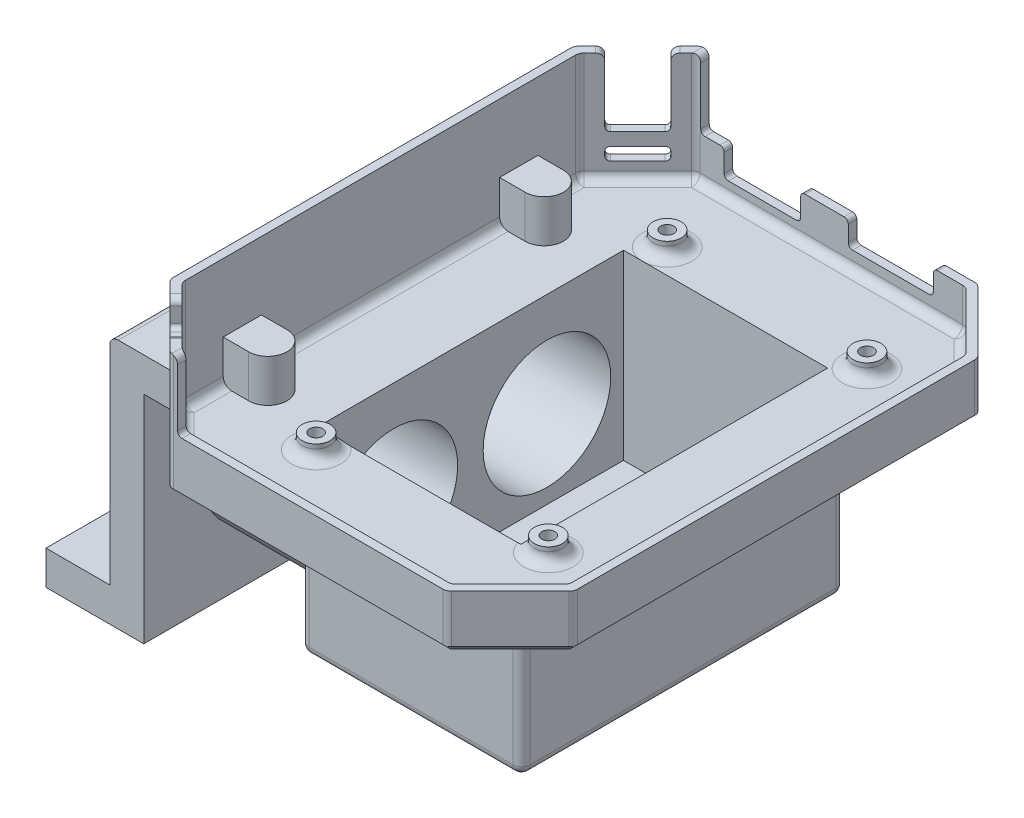
SolidWorks part; units mm, degrees
ref_plane "Front Plane" through (0, 0, 0) normal (0, 0, 1) x (1, 0, 0)
ref_plane "Top Plane" through (0, 0, 0) normal (0, 1, 0) x (1, 0, 0)
ref_plane "Right Plane" through (0, 0, 0) normal (1, 0, 0) x (0, 0, -1)
sketch "Skica1" plane through (0, 0, 0) normal (0, 1, 0) x (1, 0, 0)
  line L1 (0, 0) -> (95, 0)
  line L2 (0, 0) -> (0, 125)
  line L3 (0, 125) -> (95, 125)
  line L4 (95, 0) -> (95, 125)
  dimension "D1" = 125
  dimension "D2" = 95
extrude "Přidat vysunutím1" add sketch "Skica1" along normal blind 2.8
chamfer "Zkosení1" distance 15 angle 45 4 edges at (95, 1.4, -125) (95, 1.4, 0) (0, 1.4, 0) (0, 1.4, -125)
sketch "Skica2" plane through (0, 2.8, 0) normal (0, 1, 0) x (1, 0, 0)
  line L0 (93, 15.8284) -> (93, 109.1716)
  line L1 (93, 109.1716) -> (79.1716, 123)
  line L2 (79.1716, 123) -> (15.8284, 123)
  line L3 (15.8284, 123) -> (2, 109.1716)
  line L4 (2, 109.1716) -> (2, 15.8284)
  line L5 (2, 15.8284) -> (15.8284, 2)
  line L6 (15.8284, 2) -> (79.1716, 2)
  line L7 (79.1716, 2) -> (93, 15.8284)
  line L8 (95, 15) -> (95, 110)
  line L9 (95, 110) -> (80, 125)
  line L10 (80, 125) -> (15, 125)
  line L11 (15, 125) -> (0, 110)
  line L12 (0, 110) -> (0, 15)
  line L13 (0, 15) -> (15, 0)
  line L14 (15, 0) -> (80, 0)
  line L15 (80, 0) -> (95, 15)
  line L16 (95, 15) -> (95, 110)
  line L17 (95, 110) -> (80, 125)
  line L18 (80, 125) -> (15, 125)
  line L19 (15, 125) -> (0, 110)
  line L20 (0, 110) -> (0, 15)
  line L21 (0, 15) -> (15, 0)
  line L22 (15, 0) -> (80, 0)
  line L23 (80, 0) -> (95, 15)
  dimension "D1" = 0
  dimension "D2" = 2
extrude "Přidat vysunutím2" add sketch "Skica2" along normal blind 10
sketch "Skica3" plane through (0, 2.8, 0) normal (0, 1, 0) x (1, 0, 0)
  line L0 (50, 123) -> (50, 2) construction
  line L1 (23.33, 120) -> (76.67, 120) construction
  line L2 (23.33, 120) -> (23.33, 18.4) construction
  line L3 (23.33, 18.4) -> (76.67, 18.4) construction
  line L4 (76.67, 120) -> (76.67, 18.4) construction
  line L5 (23.33, 120) -> (76.67, 18.4) construction
  line L6 (23.33, 18.4) -> (76.67, 120) construction
  line L9 (0, 110) -> (0, 15) construction
  line L10 (79.1716, 123) -> (15.8284, 123) construction
  circle A0 centre (25.87, 106.03) radius 1.55
  circle A1 centre (74.13, 104.76) radius 1.55
  circle A2 centre (74.13, 29.83) radius 1.55
  circle A3 centre (30.95, 53.96) radius 1.55
  circle A4 centre (25.87, 23.48) radius 1.55
  point P0 (50, 69.2)
  dimension "D4" = 2.54
  dimension "D6" = 15.24
  dimension "D7" = 3.1
  dimension "D11" = 66.04
  dimension "D1" = 53.34
  dimension "D2" = 101.6
  dimension "D3" = 3
  dimension "D5" = 2.54
  dimension "D8" = 13.97
  dimension "D9" = 90.17
  dimension "D10" = 7.62
  dimension "D12" = 96.52
  dimension "D13" = 50
extrude "Odebrat vysunutím1" cut sketch "Skica3" against normal blind 10
chamfer "Zkosení2" distance 1.5 angle 45 8 edges at (87.5, 0, -117.5) (95, 0, -62.5) (87.5, 0, -7.5) (47.5, 0, 0) (7.5, 0, -7.5) (0, 0, -62.5) (7.5, 0, -117.5) (47.5, 0, -125)
fillet "Zaoblit1" radius 2 24 edges at (93, 7.8, -15.8284) (79.1716, 7.8, -2) (15.8284, 7.8, -2) (2, 7.8, -15.8284) (15.8284, 7.8, -123) (2, 7.8, -109.1716) (93, 7.8, -109.1716) (79.1716, 7.8, -123) (8.9142, 2.8, -8.9142) (47.5, 2.8, -2) (86.0858, 2.8, -8.9142) (93, 2.8, -62.5) (86.0858, 2.8, -116.0858) (47.5, 2.8, -123) (2, 2.8, -62.5) (8.9142, 2.8, -116.0858) (15, 7.15, 0) (0, 7.15, -15) (0, 7.15, -110) (15, 7.15, -125) (80, 7.15, -125) (95, 7.15, -110) (95, 7.15, -15) (80, 7.15, 0)
sketch "Skica5" plane through (0, 2.8, 0) normal (0, 1, 0) x (1, 0, 0)
  circle A0 centre (74.13, 29.83) radius 3.3
  circle A1 centre (25.87, 23.48) radius 3.3
  circle A2 centre (30.95, 53.96) radius 3.3
  circle A3 centre (25.87, 106.03) radius 3.3
  circle A4 centre (74.13, 104.76) radius 3.3
  circle A5 centre (25.87, 23.48) radius 1.55 construction
  circle A6 centre (74.13, 29.83) radius 1.55 construction
  circle A7 centre (30.95, 53.96) radius 1.55 construction
  circle A8 centre (25.87, 106.03) radius 1.55 construction
  circle A9 centre (74.13, 104.76) radius 1.55 construction
  circle A10 centre (25.87, 23.48) radius 1.55
  circle A11 centre (74.13, 29.83) radius 1.55
  circle A12 centre (30.95, 53.96) radius 1.55
  circle A13 centre (25.87, 106.03) radius 1.55
  circle A14 centre (74.13, 104.76) radius 1.55
  dimension "D1" = 6.6
extrude "Přidat vysunutím3" add sketch "Skica5" along normal blind 3.5
fillet "Zaoblit2" radius 2.5 5 edges at (74.13, 2.8, -108.06) (25.87, 2.8, -109.33) (30.95, 2.8, -57.26) (25.87, 2.8, -26.78) (74.13, 2.8, -33.13)
sketch "Skica6" plane through (0, 0, 0) normal (0, -1, 0) x (1, 0, 0)
  line L1 (75.6311, -107.36) -> (77.1322, -104.76)
  line L2 (77.1322, -104.76) -> (75.6311, -102.16)
  line L3 (75.6311, -102.16) -> (72.6289, -102.16)
  line L4 (72.6289, -102.16) -> (71.1278, -104.76)
  line L5 (71.1278, -104.76) -> (72.6289, -107.36)
  line L6 (72.6289, -107.36) -> (75.6311, -107.36)
  line L7 (27.3711, -108.63) -> (28.8722, -106.03)
  line L8 (28.8722, -106.03) -> (27.3711, -103.43)
  line L9 (27.3711, -103.43) -> (24.3689, -103.43)
  line L10 (24.3689, -103.43) -> (22.8678, -106.03)
  line L11 (22.8678, -106.03) -> (24.3689, -108.63)
  line L12 (24.3689, -108.63) -> (27.3711, -108.63)
  line L13 (32.4511, -56.56) -> (33.9522, -53.96)
  line L14 (33.9522, -53.96) -> (32.4511, -51.36)
  line L15 (32.4511, -51.36) -> (29.4489, -51.36)
  line L16 (29.4489, -51.36) -> (27.9478, -53.96)
  line L17 (27.9478, -53.96) -> (29.4489, -56.56)
  line L18 (29.4489, -56.56) -> (32.4511, -56.56)
  line L19 (27.3711, -26.08) -> (28.8722, -23.48)
  line L20 (28.8722, -23.48) -> (27.3711, -20.88)
  line L21 (27.3711, -20.88) -> (24.3689, -20.88)
  line L22 (24.3689, -20.88) -> (22.8678, -23.48)
  line L23 (22.8678, -23.48) -> (24.3689, -26.08)
  line L24 (24.3689, -26.08) -> (27.3711, -26.08)
  line L25 (75.6311, -32.43) -> (77.1322, -29.83)
  line L26 (77.1322, -29.83) -> (75.6311, -27.23)
  line L27 (75.6311, -27.23) -> (72.6289, -27.23)
  line L28 (72.6289, -27.23) -> (71.1278, -29.83)
  line L29 (71.1278, -29.83) -> (72.6289, -32.43)
  line L30 (72.6289, -32.43) -> (75.6311, -32.43)
  circle A0 centre (74.13, -104.76) radius 2.6 construction
  circle A1 centre (25.87, -106.03) radius 2.6 construction
  circle A2 centre (30.95, -53.96) radius 2.6 construction
  circle A3 centre (25.87, -23.48) radius 2.6 construction
  circle A4 centre (74.13, -29.83) radius 2.6 construction
  dimension "D1" = 5.2
extrude "Odebrat vysunutím2" cut sketch "Skica6" against normal blind 2.5
sketch "Skica8" plane through (0, 12.8, 0) normal (0, 1, 0) x (1, 0, 0)
  line L1 (2, 108.3431) -> (2, 16.6569) construction
  line L2 (2, 108.3431) -> (2, 16.6569)
  line L4 (0, 15.8284) -> (0, 109.1716)
  line L5 (2.5858, 15.2426) -> (15.2426, 2.5858) construction
  line L6 (0.5858, 14.4142) -> (14.4142, 0.5858) construction
  line L7 (2.5858, 15.2426) -> (15.2426, 2.5858)
  line L8 (0.5858, 14.4142) -> (14.4142, 0.5858)
  line L10 (15.8284, 0) -> (79.1716, 0) construction
  line L11 (15.8284, 0) -> (16.8, 0)
  line L12 (95, 62.5) -> (0, 62.5) construction
  line L13 (95, 15.8284) -> (95, 109.1716) construction
  line L14 (15.8284, 125) -> (16.8, 125)
  line L16 (0.5858, 110.5858) -> (14.4142, 124.4142)
  line L17 (2.5858, 109.7574) -> (15.2426, 122.4142)
  line L21 (16.8, 125) -> (16.8, 123)
  line L22 (16.6569, 123) -> (78.3431, 123) construction
  line L24 (16.8, 0) -> (16.8, 2.0051)
  line L25 (16.8, 123) -> (16.8, 122.9949)
  arc A0 (0, 15.8284) -> (0.5858, 14.4142) centre (2, 15.8284) ccw construction
  arc A1 (2, 16.6569) -> (2.5858, 15.2426) centre (4, 16.6569) ccw construction
  arc A2 (0, 15.8284) -> (0.5858, 14.4142) centre (2, 15.8284) ccw
  arc A3 (2, 16.6569) -> (2.5858, 15.2426) centre (4, 16.6569) ccw
  arc A4 (14.4142, 0.5858) -> (15.8284, 0) centre (15.8284, 2) ccw construction
  arc A5 (15.2426, 2.5858) -> (16.6569, 2) centre (16.6569, 4) ccw construction
  arc A6 (14.4142, 0.5858) -> (15.8284, 0) centre (15.8284, 2) ccw
  arc A7 (15.2426, 2.5858) -> (16.8, 2.0051) centre (16.6569, 4) ccw
  arc A8 (15.2426, 122.4142) -> (16.8, 122.9949) centre (16.6569, 121) cw
  arc A9 (14.4142, 124.4142) -> (15.8284, 125) centre (15.8284, 123) cw
  arc A10 (2, 108.3431) -> (2.5858, 109.7574) centre (4, 108.3431) cw
  arc A11 (0, 109.1716) -> (0.5858, 110.5858) centre (2, 109.1716) cw
  dimension "D1" = 16.8
  dimension "D2" = 16.8
extrude "Přidat vysunutím5" add sketch "Skica8" along normal blind 16
sketch "Skica11" plane through (0, 0, -125) normal (0, 0, -1) x (-1, 0, 0)
  line L0 (-79.1716, 12.8) -> (-16.8, 12.8) construction
  line L1 (-71.5, 12.8) -> (-51.5, 12.8)
  line L2 (-71.5, 12.8) -> (-71.5, 7)
  line L3 (-71.5, 7) -> (-51.5, 7)
  line L4 (-51.5, 12.8) -> (-51.5, 7)
  line L5 (-15.6213, 0) -> (-79.3787, 0) construction
  line L6 (-95, 1.5) -> (-95, 12.8) construction
  line L9 (-40.307, 12.8) -> (-22.307, 12.8)
  line L10 (-40.307, 12.8) -> (-40.307, 6.5)
  line L11 (-40.307, 6.5) -> (-22.307, 6.5)
  line L12 (-22.307, 12.8) -> (-22.307, 6.5)
  point P8 (-61.5, 7)
  point P11 (-31.307, 6.5)
  dimension "D1" = 7
  dimension "D2" = 33.5
  dimension "D3" = 20
  dimension "D4" = 30.193
  dimension "D5" = 18
  dimension "D6" = 6.5
extrude "Odebrat vysunutím3" cut sketch "Skica11" against normal blind 10
fillet "Zaoblit5" radius 1 10 edges at (22.307, 12.8, -124) (22.307, 6.5, -124) (40.307, 6.5, -124) (40.307, 12.8, -124) (51.5, 12.8, -124) (51.5, 7, -124) (71.5, 7, -124) (71.5, 12.8, -124) (16.8, 12.8, -1) (16.8, 12.8, -124)
sketch "Skica14" plane through (-55, 0, -55) normal (-0.7071, 0, -0.7071) x (-0.7071, 0, 0.7071)
  line L0 (-98.1665, 28.8) -> (-78.6102, 28.8) construction
  line L1 (-93.8883, 44.8) -> (-82.8883, 44.8)
  line L2 (-93.8883, 44.8) -> (-93.8883, 12.8)
  line L3 (-93.8883, 12.8) -> (-82.8883, 12.8)
  line L4 (-82.8883, 44.8) -> (-82.8883, 12.8)
  line L5 (-93.8883, 44.8) -> (-82.8883, 12.8) construction
  line L6 (-93.8883, 12.8) -> (-82.8883, 44.8) construction
  line L8 (-93.8883, 9.8) -> (-82.8883, 9.8)
  line L9 (-93.8883, 9.8) -> (-93.8883, 6.8)
  line L10 (-93.8883, 6.8) -> (-82.8883, 6.8)
  line L11 (-82.8883, 9.8) -> (-82.8883, 6.8)
  line L12 (-93.8883, 9.8) -> (-82.8883, 6.8) construction
  line L13 (-93.8883, 6.8) -> (-82.8883, 9.8) construction
  point P0 (-88.3883, 28.8)
  point P7 (-88.3883, 8.3)
  dimension "D1" = 11
  dimension "D2" = 16
  dimension "D3" = 3
  dimension "D4" = 3
extrude "Odebrat vysunutím6" cut sketch "Skica14" against normal blind 3.5
sketch "Skica15" plane through (7.5, 0, -7.5) normal (-0.7071, 0, 0.7071) x (0.7071, 0, 0.7071)
  line L0 (-9.7782, 28.8) -> (9.7782, 28.8) construction
  line L1 (-5, 34.8) -> (5, 34.8)
  line L2 (-5, 34.8) -> (-5, 22.8)
  line L3 (-5, 22.8) -> (5, 22.8)
  line L4 (5, 34.8) -> (5, 22.8)
  line L5 (-5, 34.8) -> (5, 22.8) construction
  line L6 (-5, 22.8) -> (5, 34.8) construction
  line L8 (-5, 16.8) -> (5, 16.8)
  line L9 (-5, 16.8) -> (-5, 13.8)
  line L10 (-5, 13.8) -> (5, 13.8)
  line L11 (5, 16.8) -> (5, 13.8)
  line L12 (-5, 16.8) -> (5, 13.8) construction
  line L13 (-5, 13.8) -> (5, 16.8) construction
  point P0 (0, 28.8)
  point P7 (0, 15.3)
  dimension "D1" = 10
  dimension "D2" = 6
  dimension "D3" = 6
  dimension "D4" = 3
extrude "Odebrat vysunutím7" cut sketch "Skica15" against normal blind 3.5
fillet "Zaoblit6" radius 1 12 edges at (12.0962, 12.8, -120.682) (4.318, 12.8, -112.9038) (4.318, 6.8, -112.9038) (4.318, 9.8, -112.9038) (12.0962, 6.8, -120.682) (12.0962, 9.8, -120.682) (11.7426, 16.8, -4.6716) (11.7426, 13.8, -4.6716) (4.6716, 13.8, -11.7426) (4.6716, 16.8, -11.7426) (11.7426, 22.8, -4.6716) (4.6716, 22.8, -11.7426)
sketch "Skica17" plane through (0, 0, 0) normal (0, -1, 0) x (-1, 0, 0)
  line L1 (-27.0824, 21.38) -> (-24.6576, 21.38)
  line L2 (-24.6576, 21.38) -> (-23.4451, 23.48)
  line L3 (-23.4451, 23.48) -> (-24.6576, 25.58)
  line L4 (-24.6576, 25.58) -> (-27.0824, 25.58)
  line L5 (-27.0824, 25.58) -> (-28.2949, 23.48)
  line L6 (-28.2949, 23.48) -> (-27.0824, 21.38)
  line L7 (-27.3711, 20.88) -> (-24.3689, 20.88) construction
  line L8 (-75.6311, 102.16) -> (-72.6289, 102.16) construction
  line L9 (-75.3424, 27.73) -> (-72.9176, 27.73)
  line L10 (-72.9176, 27.73) -> (-71.7051, 29.83)
  line L11 (-71.7051, 29.83) -> (-72.9176, 31.93)
  line L12 (-72.9176, 31.93) -> (-75.3424, 31.93)
  line L13 (-75.3424, 31.93) -> (-76.5549, 29.83)
  line L14 (-76.5549, 29.83) -> (-75.3424, 27.73)
  line L15 (-32.1624, 51.86) -> (-29.7376, 51.86)
  line L16 (-29.7376, 51.86) -> (-28.5251, 53.96)
  line L17 (-28.5251, 53.96) -> (-29.7376, 56.06)
  line L18 (-29.7376, 56.06) -> (-32.1624, 56.06)
  line L19 (-32.1624, 56.06) -> (-33.3749, 53.96)
  line L20 (-33.3749, 53.96) -> (-32.1624, 51.86)
  line L21 (-27.0824, 103.93) -> (-24.6576, 103.93)
  line L22 (-24.6576, 103.93) -> (-23.4451, 106.03)
  line L23 (-23.4451, 106.03) -> (-24.6576, 108.13)
  line L24 (-24.6576, 108.13) -> (-27.0824, 108.13)
  line L25 (-27.0824, 108.13) -> (-28.2949, 106.03)
  line L26 (-28.2949, 106.03) -> (-27.0824, 103.93)
  line L27 (-75.3424, 102.66) -> (-72.9176, 102.66)
  line L28 (-72.9176, 102.66) -> (-71.7051, 104.76)
  line L29 (-71.7051, 104.76) -> (-72.9176, 106.86)
  line L30 (-72.9176, 106.86) -> (-75.3424, 106.86)
  line L31 (-75.3424, 106.86) -> (-76.5549, 104.76)
  line L32 (-76.5549, 104.76) -> (-75.3424, 102.66)
  line L33 (-27.3711, 103.43) -> (-24.3689, 103.43) construction
  line L34 (-75.6311, 27.23) -> (-72.6289, 27.23) construction
  line L35 (-32.4511, 51.36) -> (-29.4489, 51.36) construction
  circle A0 centre (-25.87, 23.48) radius 2.1 construction
  circle A1 centre (-74.13, 29.83) radius 2.1 construction
  circle A2 centre (-30.95, 53.96) radius 2.1 construction
  circle A3 centre (-25.87, 106.03) radius 2.1 construction
  circle A4 centre (-74.13, 104.76) radius 2.1 construction
  dimension "D1" = 0.5
extrude "SUPP1" [suppressed] add sketch "Skica17" against normal blind 1 separate body contours L1 L2 L3 L4 L5 L6
sketch "Skica18" [suppressed] plane through (0, 1, 0) normal (0, 1, 0) x (1, 0, 0)
  line L0 (24.8134, 35.98) -> (26.2568, 38.48) construction
  line L1 (26.2568, 38.48) -> (24.8134, 40.98) construction
  line L2 (24.8134, 40.98) -> (21.9266, 40.98) construction
  line L3 (21.9266, 40.98) -> (20.4832, 38.48) construction
  line L4 (20.4832, 38.48) -> (21.9266, 35.98) construction
  line L5 (21.9266, 35.98) -> (24.8134, 35.98) construction
  line L6 (73.0734, 42.33) -> (74.5168, 44.83) construction
  line L7 (74.5168, 44.83) -> (73.0734, 47.33) construction
  line L8 (73.0734, 47.33) -> (70.1866, 47.33) construction
  line L9 (70.1866, 47.33) -> (68.7432, 44.83) construction
  line L10 (68.7432, 44.83) -> (70.1866, 42.33) construction
  line L11 (70.1866, 42.33) -> (73.0734, 42.33) construction
  line L12 (29.8934, 66.46) -> (31.3368, 68.96) construction
  line L13 (31.3368, 68.96) -> (29.8934, 71.46) construction
  line L14 (29.8934, 71.46) -> (27.0066, 71.46) construction
  line L15 (27.0066, 71.46) -> (25.5632, 68.96) construction
  line L16 (25.5632, 68.96) -> (27.0066, 66.46) construction
  line L17 (27.0066, 66.46) -> (29.8934, 66.46) construction
  line L18 (24.8134, 118.53) -> (26.2568, 121.03) construction
  line L19 (26.2568, 121.03) -> (24.8134, 123.53) construction
  line L20 (24.8134, 123.53) -> (21.9266, 123.53) construction
  line L21 (21.9266, 123.53) -> (20.4832, 121.03) construction
  line L22 (20.4832, 121.03) -> (21.9266, 118.53) construction
  line L23 (21.9266, 118.53) -> (24.8134, 118.53) construction
  line L24 (73.0734, 117.26) -> (74.5168, 119.76) construction
  line L25 (74.5168, 119.76) -> (73.0734, 122.26) construction
  line L26 (73.0734, 122.26) -> (70.1866, 122.26) construction
  line L27 (70.1866, 122.26) -> (68.7432, 119.76) construction
  line L28 (68.7432, 119.76) -> (70.1866, 117.26) construction
  line L29 (70.1866, 117.26) -> (73.0734, 117.26) construction
  line L30 (24.8134, 35.98) -> (26.2568, 38.48)
  line L31 (26.2568, 38.48) -> (24.8134, 40.98)
  line L32 (24.8134, 40.98) -> (21.9266, 40.98)
  line L33 (21.9266, 40.98) -> (20.4832, 38.48)
  line L34 (20.4832, 38.48) -> (21.9266, 35.98)
  line L35 (21.9266, 35.98) -> (24.8134, 35.98)
  line L36 (73.0734, 42.33) -> (74.5168, 44.83)
  line L37 (74.5168, 44.83) -> (73.0734, 47.33)
  line L38 (73.0734, 47.33) -> (70.1866, 47.33)
  line L39 (70.1866, 47.33) -> (68.7432, 44.83)
  line L40 (68.7432, 44.83) -> (70.1866, 42.33)
  line L41 (70.1866, 42.33) -> (73.0734, 42.33)
  line L42 (29.8934, 66.46) -> (31.3368, 68.96)
  line L43 (31.3368, 68.96) -> (29.8934, 71.46)
  line L44 (29.8934, 71.46) -> (27.0066, 71.46)
  line L45 (27.0066, 71.46) -> (25.5632, 68.96)
  line L46 (25.5632, 68.96) -> (27.0066, 66.46)
  line L47 (27.0066, 66.46) -> (29.8934, 66.46)
  line L48 (24.8134, 118.53) -> (26.2568, 121.03)
  line L49 (26.2568, 121.03) -> (24.8134, 123.53)
  line L50 (24.8134, 123.53) -> (21.9266, 123.53)
  line L51 (21.9266, 123.53) -> (20.4832, 121.03)
  line L52 (20.4832, 121.03) -> (21.9266, 118.53)
  line L53 (21.9266, 118.53) -> (24.8134, 118.53)
  line L54 (73.0734, 117.26) -> (74.5168, 119.76)
  line L55 (74.5168, 119.76) -> (73.0734, 122.26)
  line L56 (73.0734, 122.26) -> (70.1866, 122.26)
  line L57 (70.1866, 122.26) -> (68.7432, 119.76)
  line L58 (68.7432, 119.76) -> (70.1866, 117.26)
  line L59 (70.1866, 117.26) -> (73.0734, 117.26)
  line L60 (24.5824, 36.38) -> (25.7949, 38.48)
  line L61 (25.7949, 38.48) -> (24.5824, 40.58)
  line L62 (24.5824, 40.58) -> (22.1576, 40.58)
  line L63 (22.1576, 40.58) -> (20.9451, 38.48)
  line L64 (20.9451, 38.48) -> (22.1576, 36.38)
  line L65 (22.1576, 36.38) -> (24.5824, 36.38)
  line L66 (72.8424, 42.73) -> (74.0549, 44.83)
  line L67 (74.0549, 44.83) -> (72.8424, 46.93)
  line L68 (72.8424, 46.93) -> (70.4176, 46.93)
  line L69 (70.4176, 46.93) -> (69.2051, 44.83)
  line L70 (69.2051, 44.83) -> (70.4176, 42.73)
  line L71 (70.4176, 42.73) -> (72.8424, 42.73)
  line L72 (29.6624, 66.86) -> (30.8749, 68.96)
  line L73 (30.8749, 68.96) -> (29.6624, 71.06)
  line L74 (29.6624, 71.06) -> (27.2376, 71.06)
  line L75 (27.2376, 71.06) -> (26.0251, 68.96)
  line L76 (26.0251, 68.96) -> (27.2376, 66.86)
  line L77 (27.2376, 66.86) -> (29.6624, 66.86)
  line L78 (24.5824, 118.93) -> (25.7949, 121.03)
  line L79 (25.7949, 121.03) -> (24.5824, 123.13)
  line L80 (24.5824, 123.13) -> (22.1576, 123.13)
  line L81 (22.1576, 123.13) -> (20.9451, 121.03)
  line L82 (20.9451, 121.03) -> (22.1576, 118.93)
  line L83 (22.1576, 118.93) -> (24.5824, 118.93)
  line L84 (72.8424, 117.66) -> (74.0549, 119.76)
  line L85 (74.0549, 119.76) -> (72.8424, 121.86)
  line L86 (72.8424, 121.86) -> (70.4176, 121.86)
  line L87 (70.4176, 121.86) -> (69.2051, 119.76)
  line L88 (69.2051, 119.76) -> (70.4176, 117.66)
  line L89 (70.4176, 117.66) -> (72.8424, 117.66)
  dimension "D1" = 0.4
extrude "SUPP2" [suppressed] add sketch "Skica18" along normal blind 1.8
fillet "Zaoblit8" radius 1.5 6 edges at (16.8, 28.8, -1.0026) (16.8, 28.8, -123.9974) (12.0962, 28.8, -120.682) (4.318, 28.8, -112.9038) (11.7426, 28.8, -4.6716) (4.6716, 28.8, -11.7426)
sketch "Skica20" plane through (0, 2.8, 0) normal (0, 1, 0) x (1, 0, 0)
  line L0 (21.307, 125) -> (17.8, 125) construction
  line L1 (0, 109.1716) -> (0, 15.8284) construction
  line L2 (17.8, 0) -> (79.1716, 0) construction
  line L3 (8, 34.5) -> (2, 34.5)
  line L4 (2, 16.6569) -> (2, 108.3431) construction
  line L5 (8, 25.5) -> (2, 25.5)
  line L6 (2, 25.5) -> (2, 34.5)
  line L7 (2, 16.6569) -> (2, 108.3431) construction
  line L8 (8, 99.5) -> (2, 99.5)
  line L9 (2, 16.6569) -> (2, 108.3431) construction
  line L10 (8, 90.5) -> (2, 90.5)
  line L11 (2, 16.6569) -> (2, 108.3431) construction
  line L12 (2, 90.5) -> (2, 99.5)
  arc A0 (8, 90.5) -> (8, 99.5) centre (8, 95) ccw
  arc A1 (8, 25.5) -> (8, 34.5) centre (8, 30) ccw
  dimension "D3" = 9
  dimension "D1" = 30
  dimension "D2" = 8
  dimension "D4" = 30
extrude "Přidat vysunutím10" add sketch "Skica20" along normal blind 10
ref_plane "Rovina2" through (47.5, 0, 0) normal (1, 0, 0) x (0, 0, -1)
sketch "Skica29" plane through (0, 2.5, 0) normal (0, -1, 0) x (1, 0, 0)
  circle A0 centre (25.87, -106.03) radius 1.55 construction
  circle A1 centre (74.13, -104.76) radius 1.55 construction
  circle A2 centre (30.95, -53.96) radius 1.55 construction
  circle A3 centre (74.13, -29.83) radius 1.55 construction
  circle A4 centre (25.87, -23.48) radius 1.55 construction
  circle A5 centre (25.87, -106.03) radius 1.55
  circle A6 centre (74.13, -104.76) radius 1.55
  circle A7 centre (30.95, -53.96) radius 1.55
  circle A8 centre (74.13, -29.83) radius 1.55
  circle A9 centre (25.87, -23.48) radius 1.55
extrude "Přidat vysunutím14" add sketch "Skica29" against normal blind 0.2
sketch "Esboço2" plane through (0, 0, 0) normal (0, -1, 0) x (1, 0, 0)
  line L1 (21.3853, -28.2485) -> (69.3853, -28.2485)
  line L2 (21.3853, -28.2485) -> (21.3853, -100.2485)
  line L3 (21.3853, -100.2485) -> (69.3853, -100.2485)
  line L4 (69.3853, -28.2485) -> (69.3853, -100.2485)
  dimension "D1" = 72
  dimension "D2" = 48
extrude "Corte-extrusão1" cut sketch "Esboço2" against normal blind 71 contours L2 L1 L4 L3
sketch "Esboço3" plane through (0, 0, 0) normal (0, -1, 0) x (1, 0, 0)
  line L4 (71.3853, -26.2485) -> (19.3853, -26.2485)
  line L5 (19.3853, -26.2485) -> (19.3853, -102.2485)
  line L6 (19.3853, -102.2485) -> (71.3853, -102.2485)
  line L7 (71.3853, -102.2485) -> (71.3853, -26.2485)
  line L8 (21.3853, -28.2485) -> (21.3853, -100.2485)
  line L9 (21.3853, -100.2485) -> (69.3853, -100.2485)
  line L10 (69.3853, -100.2485) -> (69.3853, -28.2485)
  line L11 (69.3853, -28.2485) -> (21.3853, -28.2485)
  line L12 (21.3853, -28.2485) -> (21.3853, -100.2485)
  line L13 (21.3853, -100.2485) -> (69.3853, -100.2485)
  line L14 (69.3853, -100.2485) -> (69.3853, -28.2485)
  line L15 (69.3853, -28.2485) -> (21.3853, -28.2485)
  dimension "D1" = 0
  dimension "D2" = 2
extrude "Ressalto-extrusão1" add sketch "Esboço3" along normal blind 40
sketch "Esboço4" plane through (0, -40, 0) normal (0, -1, 0) x (1, 0, 0)
  line L8 (71.3853, -102.2485) -> (71.3853, -26.2485)
  line L9 (71.3853, -26.2485) -> (19.3853, -26.2485)
  line L10 (19.3853, -26.2485) -> (19.3853, -102.2485)
  line L11 (19.3853, -102.2485) -> (71.3853, -102.2485)
  line L12 (71.3853, -102.2485) -> (71.3853, -26.2485)
  line L13 (71.3853, -26.2485) -> (19.3853, -26.2485)
  line L14 (19.3853, -26.2485) -> (19.3853, -102.2485)
  line L15 (19.3853, -102.2485) -> (71.3853, -102.2485)
  dimension "D1" = 0
extrude "Ressalto-extrusão2" add sketch "Esboço4" along normal blind 3
fillet "Filete1" radius 2 8 edges at (71.3853, -43, -64.2485) (45.3853, -43, -102.2485) (71.3853, -21.5, -102.2485) (71.3853, -21.5, -26.2485) (45.3853, -43, -26.2485) (19.3853, -21.5, -26.2485) (19.3853, -43, -64.2485) (19.3853, -21.5, -102.2485)
sketch "Esboço7" plane through (0, 0, 0) normal (-1, 0, 0) x (0, 0, 1)
  line L0 (-15.8284, 1.5) -> (-15.8284, 28.8) construction
  line L1 (-109.1716, 1.5) -> (-15.8284, 1.5)
  line L2 (-109.1716, 1.5) -> (-109.1716, 9.5)
  line L3 (-109.1716, 9.5) -> (-15.8284, 9.5)
  line L4 (-15.8284, 1.5) -> (-15.8284, 9.5)
  dimension "D1" = 8
extrude "Ressalto-extrusão3" add sketch "Esboço7" along normal blind 15
sketch "Esboço8" plane through (0, 1.5, 0) normal (0, -1, 0) x (1, 0, 0)
  line L0 (-15, -15.8284) -> (0, -15.8284) construction
  line L1 (-15, -109.1716) -> (-7, -109.1716)
  line L2 (-15, -109.1716) -> (-15, -15.8284)
  line L3 (-15, -15.8284) -> (-7, -15.8284)
  line L4 (-7, -109.1716) -> (-7, -15.8284)
  dimension "D1" = 8
extrude "Ressalto-extrusão4" add sketch "Esboço8" along normal up to vertex (50.8526 mm away)
sketch "Esboço9" plane through (-15, 0, 0) normal (-1, 0, 0) x (0, 0, 1)
  line L0 (-15.8284, -49.3526) -> (-15.8284, 9.5) construction
  line L1 (-109.1716, -49.3526) -> (-15.8284, -49.3526)
  line L2 (-109.1716, -49.3526) -> (-109.1716, -41.3526)
  line L3 (-109.1716, -41.3526) -> (-15.8284, -41.3526)
  line L4 (-15.8284, -49.3526) -> (-15.8284, -41.3526)
  dimension "D1" = 8
extrude "Ressalto-extrusão5" add sketch "Esboço9" along normal blind 15
sketch "Esboço10" plane through (0, -41.3526, 0) normal (0, 1, 0) x (1, 0, 0)
  line L0 (-22.5, 109.1716) -> (-22.5, 15.8284) construction
  line L1 (-30, 109.1716) -> (-15, 109.1716) construction
  line L2 (-30, 15.8284) -> (-15, 15.8284) construction
  circle A0 centre (-22.5, 94.1716) radius 3
  circle A1 centre (-22.5, 30.8284) radius 3
  point P8 (0, 0)
  point P11 (0, 0)
  dimension "D1" = 6
  dimension "D2" = 15
  dimension "D3" = 15
extrude "Corte-extrusão3" cut sketch "Esboço10" against normal through all
fillet "Filete2" radius 2 1 edges at (-15, 9.5, -62.5)
sketch "Esboço6" plane through (19.3853, 0, 0) normal (-1, 0, 0) x (0, 0, 1)
  circle A9 centre (-46.2485, -21.5) radius 15
  circle A12 centre (-82.2485, -21.5) radius 15
extrude "Corte-extrusão2" cut sketch "Esboço6" against normal blind 10 and the other way blind 50
sketch "Esboço11" plane through (19.3853, 0, 0) normal (-1, 0, 0) x (0, 0, 1)
  circle A2 centre (-46.2485, -21.5) radius 17
  circle A3 centre (-46.2485, -21.5) radius 17
  circle A5 centre (-82.2485, -21.5) radius 17
  circle A6 centre (-82.2485, -21.5) radius 17
  circle A8 centre (-82.2485, -21.5) radius 15
  circle A9 centre (-82.2485, -21.5) radius 15
  circle A11 centre (-46.2485, -21.5) radius 15
  circle A12 centre (-46.2485, -21.5) radius 15
  dimension "D1" = 2
  dimension "D2" = 2
  dimension "D3" = 0
  dimension "D4" = 0
extrude "Ressalto-extrusão6" add sketch "Esboço11" along normal up to vertex (26.3853 mm away)
fillet "Filete3" radius 2 2 edges at (-15, -21.5, -61.2485) (-15, -21.5, -97.2485)
